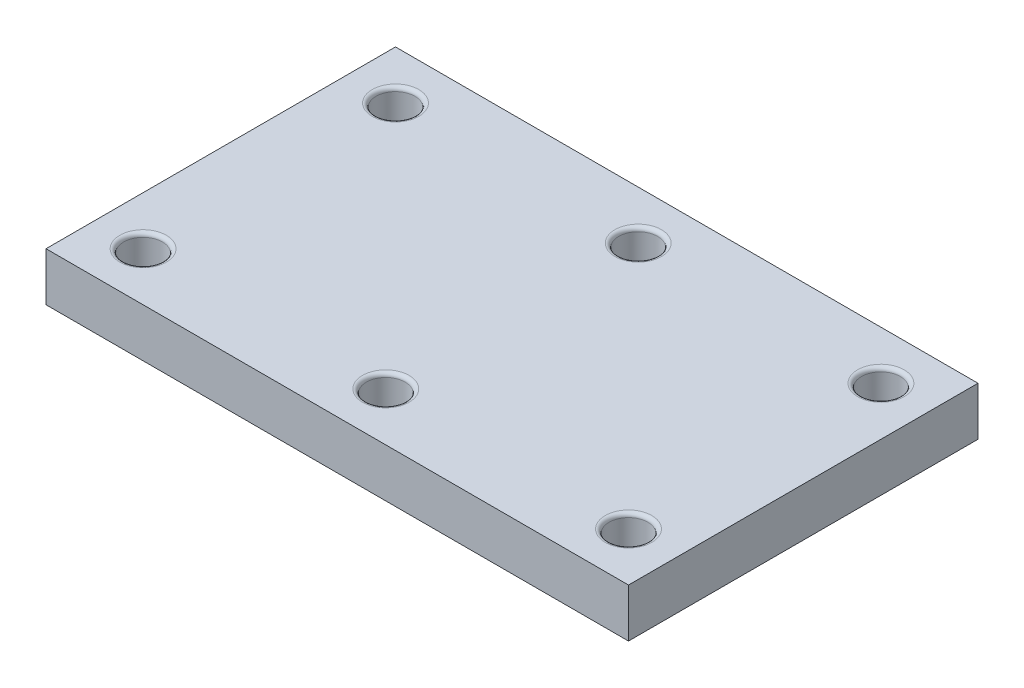
SolidWorks part; units mm, degrees
ref_plane "Front Plane" through (0, 0, 0) normal (0, 0, 1) x (1, 0, 0)
ref_plane "Top Plane" through (0, 0, 0) normal (0, 1, 0) x (1, 0, 0)
ref_plane "Right Plane" through (0, 0, 0) normal (1, 0, 0) x (0, 0, -1)
sketch "Sketch1" plane through (0, 0, 0) normal (0, 1, 0) x (1, 0, 0)
  line L1 (-150, -90) -> (150, -90)
  line L2 (-150, -90) -> (-150, 90)
  line L3 (-150, 90) -> (150, 90)
  line L4 (150, -90) -> (150, 90)
  line L5 (-150, -90) -> (150, 90) construction
  line L6 (-150, 90) -> (150, -90) construction
  point P0 (0, 0)
  dimension "D1" = 300
  dimension "D2" = 180
extrude "Boss-Extrude1" add sketch "Sketch1" along normal blind 25
sketch "Sketch2" plane through (0, 0, 0) normal (0, 1, 0) x (1, 0, 0)
  line L0 (-150, 0) -> (150, 0) construction
  line L1 (-150, 90) -> (-150, -90) construction
  line L2 (150, -90) -> (150, 90) construction
  line L3 (-150, -90) -> (150, -90) construction
  circle A1 centre (0, 65) radius 10
  circle A2 centre (125, 65) radius 10
  circle A3 centre (-125, 65) radius 10
  circle A4 centre (125, -65) radius 10
  circle A5 centre (0, -65) radius 10
  circle A6 centre (-125, -65) radius 10
  dimension "D1" = 20
  dimension "D2" = 20
  dimension "D7" = 20
  dimension "D3" = 25
  dimension "D4" = 155
  dimension "D5" = 250
  dimension "D6" = 155
  dimension "D8" = 125
  dimension "D9" = 155
extrude "Cut-Extrude4" cut sketch "Sketch2" along normal blind 212 contours A1
extrude "Cut-Extrude5" cut sketch "Sketch2<5>" along normal blind 159 contours A3
sketch "Sketch2<5>" plane through (0, 0, 0) normal (0, 1, 0) x (1, 0, 0) same geometry as "Sketch2"
extrude "Cut-Extrude6" cut sketch "Sketch2<6>" along normal blind 209 contours A2
sketch "Sketch2<6>" plane through (0, 0, 0) normal (0, 1, 0) x (1, 0, 0) same geometry as "Sketch2"
extrude "Cut-Extrude7" cut sketch "Sketch2<7>" along normal blind 305 contours A6 | A5 | A4
sketch "Sketch2<7>" plane through (0, 0, 0) normal (0, 1, 0) x (1, 0, 0) same geometry as "Sketch2"
fillet "Fillet1" radius 2 6 edges at (-125, 25, -75) (0, 25, -75) (125, 25, -75) (125, 25, 55) (0, 25, 55) (-125, 25, 55)
